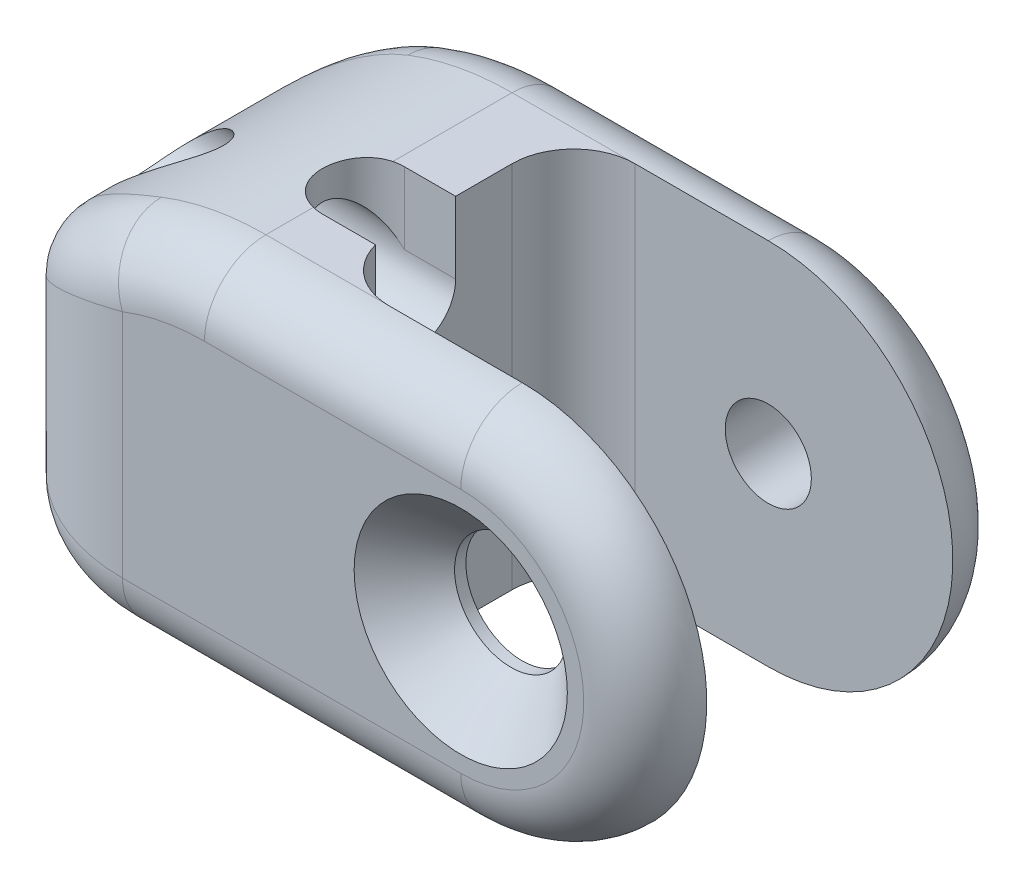
SolidWorks part; units mm, degrees
ref_plane "Front Plane" through (0, 0, 0) normal (0, 0, 1) x (1, 0, 0)
ref_plane "Top Plane" through (0, 0, 0) normal (0, 1, 0) x (1, 0, 0)
ref_plane "Right Plane" through (0, 0, 0) normal (1, 0, 0) x (0, 0, -1)
sketch "Sketch2" plane through (0, 0, 0) normal (0, 1, 0) x (1, 0, 0)
  line L0 (-2, 9) -> (23.5, 9)
  line L1 (23.5, 9) -> (23.5, 6)
  line L2 (23.5, 6) -> (8, 6)
  line L3 (5, 3) -> (5, -3)
  line L4 (8, -6) -> (23.5, -6)
  line L5 (23.5, -6) -> (23.5, -9)
  line L8 (-49.3622, 0) -> (56.3776, 0) construction
  line L9 (0, 21.2372) -> (0, -19.0689) construction
  line L10 (5, 3) -> (8, 3) construction
  line L11 (8, 3) -> (8, 6) construction
  line L16 (-2, -9) -> (23.5, -9)
  arc A0 (8, 6) -> (5, 3) centre (8, 3) ccw
  arc A1 (8, -6) -> (5, -3) centre (8, -3) cw
  arc A3 (-2, 9) -> (-2, -9) centre (-2, 0) ccw
  point P13 (8, 3)
  dimension "D2" = 18
  dimension "D3" = 3
  dimension "D4" = 18.5
  dimension "D5" = 12
  dimension "D6" = 3
  dimension "D7" = 3
  dimension "D8" = 5
  dimension "D9" = 25.5
extrude "Boss-Extrude1" add sketch "Sketch2" along normal blind 18
sketch "Sketch5" plane through (0, 0, 9) normal (0, 0, 1) x (1, 0, 0)
  line L0 (-13.5058, 9) -> (31.8434, 9) construction
  line L1 (-2, 18) -> (-2, 0) construction
  line L2 (23.5, 18) -> (23.5, 0) construction
  line L3 (-2, 18) -> (23.5, 18) construction
  line L4 (14.5, 18) -> (14.5, 0) construction
  line L5 (-11, 0) -> (-2, 0) construction
  line L7 (-12, 0) -> (-12, 4)
  line L8 (-12, 0) -> (14.5, 0)
  line L9 (2, 18) -> (14.5, 18)
  arc A1 (14.5, 0) -> (14.5, 18) centre (14.5, 9) ccw
  arc A2 (2, 18) -> (-12, 4) centre (2, 4) ccw
  dimension "D2" = 4
  dimension "D1" = 9
  dimension "D3" = 10
extrude "Cut-Extrude1" cut sketch "Sketch5" against normal blind 20 flip side to cut
sketch "Sketch6" plane through (0, 0, 9) normal (0, 0, 1) x (1, 0, 0)
  line L0 (14.5, 0) -> (14.5, 18) construction
  point P4 (14.5, 9)
hole_wizard "CSK for M5 Countersunk Flat Head Screw1" positions "Sketch7" profile "Sketch8" countersink size "M5" standard "DIN" end condition up to next
sketch "Sketch7" plane through (0, 0, 9) normal (0, 0, 1) x (1, 0, 0)
  point P0 (14.5, 9)
sketch "Sketch8" plane through (14.5, 9, 9) normal (1, 0, 0) x (0, -1, 0)
  line L0 (0, 0) -> (0, 3)
  line L1 (0, 3) -> (2.75, 3)
  line L2 (2.75, 3) -> (2.75, 2.45)
  line L3 (2.75, 2.45) -> (5.2, 0)
  line L5 (5.2, 0) -> (0, 0)
  line L6 (-2.75, 2.45) -> (-5.2, 0) construction
  line L11 (0, -6.35) -> (0, 107.95) construction
  dimension "Thru Hole Dia." = 5.5
  dimension "Thru Hole Depth" = 3
  dimension "Near C'Sink Dia." = 10.4
  dimension "Near C'Sink Angle" = 90
hole_wizard "M5 Tapped Hole1" positions "Sketch9" profile "Sketch11" tap size "M5" standard "DIN" end condition through all
sketch "Sketch9" plane through (0, 0, 9) normal (0, 0, 1) x (1, 0, 0)
  point P0 (14.5, 9)
sketch "Sketch11" plane through (14.5, 9, 9) normal (1, 0, 0) x (0, -1, 0)
  line L0 (0, 0) -> (0, 18)
  line L1 (0, 18) -> (2.1, 18)
  line L2 (2.1, 18) -> (2.1, 3.1)
  line L3 (2.1, 3.1) -> (5.2, 0)
  line L5 (5.2, 0) -> (0, 0)
  line L6 (-2.1, 3.1) -> (-5.2, 0) construction
  line L11 (0, -6.35) -> (0, 107.95) construction
  dimension "Thru Tap Drill Dia." = 4.2
  dimension "Thru Tap Drill Depth" = 18
  dimension "Near C'Sink Dia." = 10.4
  dimension "Near C'Sink Angle" = 90
cosmetic thread "Hole Thread1" parameters "D2"=5
fillet "Fillet2" radius 3 10 edges at (-10.9995, 9.1973, -0.0903) (-0.0212, 17.8533, -9) (8.25, 18, -9) (23.5, 9, -9) (-0.0212, 17.8533, 9) (8.25, 18, 9) (23.5, 9, 9) (6.25, 0, 9) (-11, 0, 0) (6.25, 0, -9)
sketch "Sketch13" plane through (5, 0, 0) normal (1, 0, 0) x (0, 0, -1)
  line L0 (-1.75, -2.2721) -> (-1.75, 20.0856) construction
  line L1 (-3, 0) -> (3, 0) construction
  line L2 (-3, 18) -> (3, 18) construction
  circle A0 centre (-1.75, 14.5) radius 2
  point P4 (0, 0)
  dimension "D2" = 3.5
  dimension "D3" = 4
  dimension "D1" = 1.75
extrude "Cut-Extrude2" cut sketch "Sketch13" against normal through all both and the other way through all
sketch "Sketch14" plane through (0, 18, 0) normal (0, 1, 0) x (1, 0, 0)
  line L0 (5, 0) -> (-14.1432, 0) construction
  line L3 (5, -3) -> (5, 3) construction
  line L4 (2.5, -3.75) -> (7.4532, -3.75)
  line L5 (2.5, 0.25) -> (7.4532, 0.25)
  line L6 (7.4532, 0.25) -> (7.4532, -3.75)
  arc A0 (2.5, 0.25) -> (2.5, -3.75) centre (2.5, -1.75) ccw
  dimension "D1" = 1.75
  dimension "D2" = 2.5
extrude "Cut-Extrude3" cut sketch "Sketch14" against normal blind 3.5
